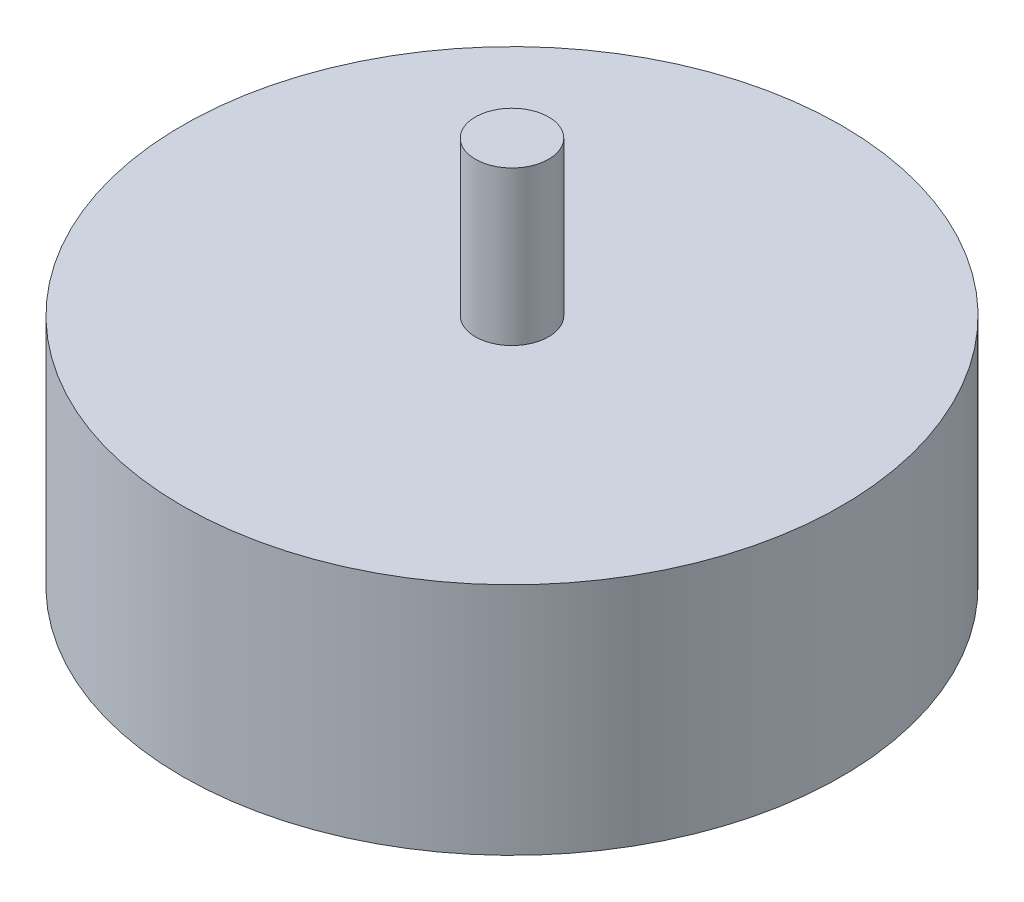
SolidWorks part; units mm, degrees
ref_plane "Front Plane" through (0, 0, 0) normal (0, 0, 1) x (1, 0, 0)
ref_plane "Top Plane" through (0, 0, 0) normal (0, 1, 0) x (1, 0, 0)
ref_plane "Right Plane" through (0, 0, 0) normal (1, 0, 0) x (0, 0, -1)
sketch "Sketch1" plane through (0, 0, 0) normal (0, 1, 0) x (1, 0, 0)
  circle A0 centre (0, 0) radius 18
  circle A1 centre (0, 0) radius 2
  dimension "D1" = 36
  dimension "D2" = 4
extrude "Boss-Extrude1" add sketch "Sketch1" along normal blind 12.8 contours A0 A1 | A1 region at (-17.4909, 0, 0) region at (0, 0, 0)
extrude "Boss-Extrude2" add sketch "Sketch1<3>" along normal blind 21.2 contours A1 region at (0, 0, 0)
sketch "Sketch1<3>" plane through (0, 0, 0) normal (0, 1, 0) x (1, 0, 0) same geometry as "Sketch1"
